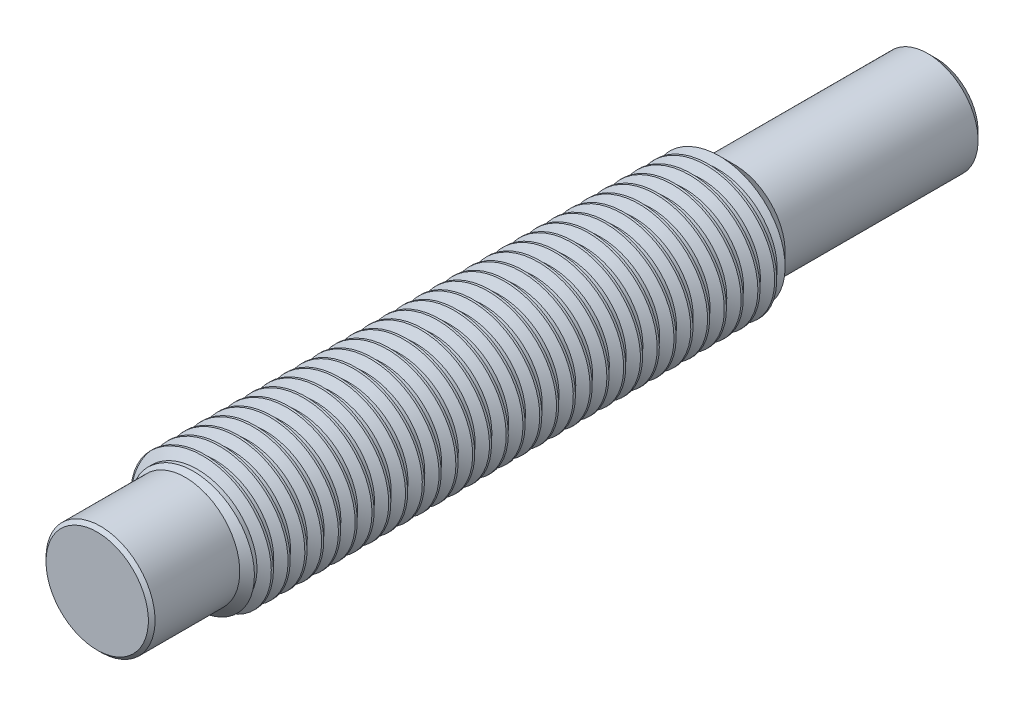
SolidWorks part; units mm, degrees
material "316 Stainless Steel"
ref_plane "Front Plane" through (0, 0, 0) normal (0, 0, 1) x (1, 0, 0)
ref_plane "Top Plane" through (0, 0, 0) normal (0, 1, 0) x (1, 0, 0)
ref_plane "Right Plane" through (0, 0, 0) normal (1, 0, 0) x (0, 0, -1)
sketch "Sketch1" plane through (0, 0, 0) normal (0, 1, 0) x (1, 0, 0)
  line L0 (0, 50) -> (-3, 50)
  line L1 (-3, 50) -> (-3, 38)
  line L2 (-3, 38) -> (-4, 38)
  line L3 (-4, 38) -> (-4, 5)
  line L4 (-3.25, 0) -> (0, 0)
  line L5 (0, 0) -> (0, 50)
  line L6 (0, 0) -> (0, -7.8138) construction
  line L7 (-3.25, 0) -> (-3.25, 5)
  line L8 (-3.25, 5) -> (-4, 5)
  dimension "D1" = 8
  dimension "D2" = 50
  dimension "D3" = 6
  dimension "D4" = 12
  dimension "D5" = 5
  dimension "D6" = 6.5
revolve "Revolve1" add sketch "Sketch1" angle 360 about L6
chamfer "Chamfer1" distance 0.2 angle 45 1 edges at (-3.25, 0, 0)
chamfer "Chamfer2" distance 1 angle 45 2 edges at (-4, 0, -38) (-4, 0, -5)
thread "Thread1" pitch 1 method cut profile "Thread Profile1" start angle 0, offset 5, length 50, pitch 1, diameter 8
ref_plane "Plane1" through (-4, 0, -1) normal (0, -1, 0) x (-1, 0, 0)
sketch "Thread Profile1" plane through (-4, 0, -1) normal (0, -1, 0) x (-1, 0, 0)
  line L0 (0, 0) -> (0, 1) construction
  line L11 (0, 0) -> (0, 0.875)
  line L12 (0, 0.875) -> (-0.5413, 0.5625)
  line L13 (-0.5413, 0.5625) -> (-0.5413, 0.3125)
  line L15 (-0.5413, 0.3125) -> (0, 0)
  line L17 (-0.5413, 0.4375) -> (0, 0.4375) construction
  point P2 (0, 0)
  dimension "Pitch" = 1
  dimension "Profile_Angle" = 60
  dimension "Profile_Land" = 0.25
  dimension "Profile_Height" = 0.5413
chamfer "Chamfer3" distance 0.5 angle 45 1 edges at (-3, 0, -50)
